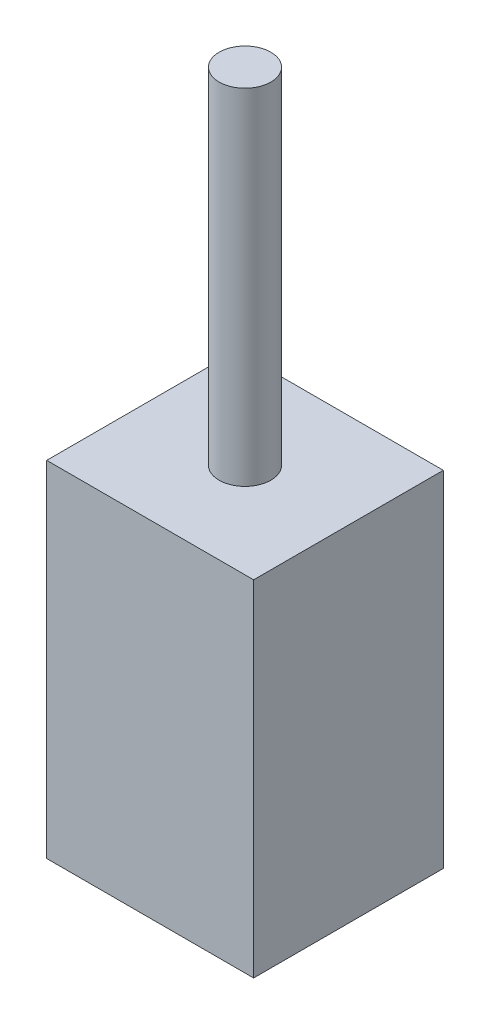
SolidWorks part; units mm, degrees
ref_plane "Front Plane" through (0, 0, 0) normal (0, 0, 1) x (1, 0, 0)
ref_plane "Top Plane" through (0, 0, 0) normal (0, 1, 0) x (1, 0, 0)
ref_plane "Right Plane" through (0, 0, 0) normal (1, 0, 0) x (0, 0, -1)
sketch "Sketch1" plane through (0, 0, 0) normal (0, 1, 0) x (1, 0, 0)
  line L1 (0, 0) -> (12, 0)
  line L2 (0, 0) -> (0, 11)
  line L3 (0, 11) -> (12, 11)
  line L4 (12, 0) -> (12, 11)
  dimension "D1" = 12
  dimension "D2" = 11
extrude "Boss-Extrude1" add sketch "Sketch1" along normal blind 20
sketch "Sketch2" plane through (0, 20, 0) normal (0, 1, 0) x (1, 0, 0)
  line L0 (-0.6033, 5.5) -> (12.6033, 5.5) construction
  line L1 (6, -0.6264) -> (6, 11.6264) construction
  line L2 (12, 11) -> (0, 11) construction
  line L3 (0, 11) -> (0, 0) construction
  circle A0 centre (6, 5.5) radius 1.5
  point P6 (6, 11)
  point P9 (0, 5.5)
  dimension "D1" = 3
extrude "Boss-Extrude2" add sketch "Sketch2" along normal blind 20
